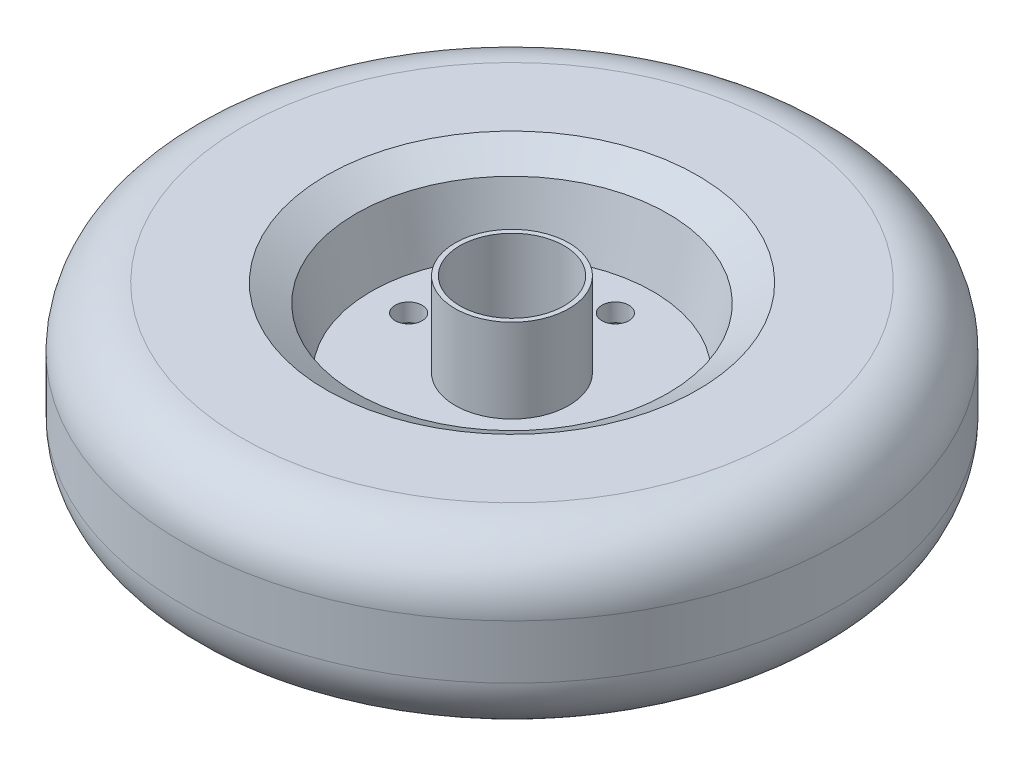
SolidWorks part; units mm, degrees
ref_plane "Alzado" through (0, 0, 0) normal (0, 0, 1) x (1, 0, 0)
ref_plane "Planta" through (0, 0, 0) normal (0, 1, 0) x (1, 0, 0)
ref_plane "Vista lateral" through (0, 0, 0) normal (1, 0, 0) x (0, 0, -1)
sketch "Croquis2" plane through (0, 0, 0) normal (0, 0, 1) x (1, 0, 0)
  line L0 (0, 31) -> (19, 31)
  line L1 (19, 31) -> (19, 3)
  line L2 (19, 3) -> (47, 3)
  line L3 (47, 3) -> (52, 23)
  line L4 (52, 23) -> (62, 29)
  line L5 (62, 29) -> (90, 29)
  line L6 (110, 9) -> (110, -9)
  line L7 (110, 0) -> (0, 0)
  line L8 (0, -31) -> (0, 31)
  line L9 (0, 64.7683) -> (0, -22.9111) construction
  line L10 (-41.779, 0) -> (154.4253, 0) construction
  line L11 (62, -29) -> (90, -29)
  line L12 (52, -23) -> (62, -29)
  line L13 (47, -3) -> (52, -23)
  line L14 (19, -3) -> (47, -3)
  line L15 (19, -31) -> (19, -3)
  line L16 (0, -31) -> (19, -31)
  arc A0 (90, 29) -> (110, 9) centre (90, 9) cw
  arc A1 (90, -29) -> (110, -9) centre (90, -9) ccw
  point P11 (110, 29)
  point P26 (110, -29)
  dimension "D10" = 20
  dimension "D1" = 19
  dimension "D2" = 28
  dimension "D3" = 48
  dimension "D4" = 10
  dimension "D5" = 5
  dimension "D6" = 29
  dimension "D7" = 28
  dimension "D8" = 3
  dimension "D9" = 20
revolve "Revolución1" add sketch "Croquis2" angle 360 about L9 region at (59.5227, 13.5557, 0) region at (59.5227, -13.5557, 0)
hole_wizard "Taladro de margen para M101" positions "Croquis3" profile "Croquis4" hole size "M10" standard "ISO" end condition through all
sketch "Croquis3" plane through (0, 31, 0) normal (0, 1, 0) x (1, 0, 0)
  point P0 (0, 0)
sketch "Croquis4" plane through (0, 31, 0) normal (1, 0, 0) x (0, 0, 1)
  line L0 (0, 0) -> (0, 62)
  line L1 (0, 62) -> (5.5, 62)
  line L2 (5.5, 62) -> (5.5, 0)
  line L5 (5.5, 0) -> (0, 0)
  line L11 (0, -6.35) -> (0, 107.95) construction
  dimension "Diámetro de taladro hasta el siguiente" = 11
  dimension "Profundidad de taladro hasta el siguiente" = 62
hole_wizard "Taladro de margen para M81" positions "Croquis5" profile "Croquis6" hole size "M8" standard "ISO" end condition through all
sketch "Croquis5" plane through (0, 3, 0) normal (0, 1, 0) x (1, 0, 0)
  point P0 (0, 34.5)
  dimension "D1" = 34.5
sketch "Croquis6" plane through (0, 3, -34.5) normal (1, 0, 0) x (0, 0, 1)
  line L0 (0, 0) -> (0, 34)
  line L1 (0, 34) -> (4.5, 34)
  line L2 (4.5, 34) -> (4.5, 0)
  line L5 (4.5, 0) -> (0, 0)
  line L11 (0, -6.35) -> (0, 107.95) construction
  dimension "Diámetro de taladro hasta el siguiente" = 9
  dimension "Profundidad de taladro hasta el siguiente" = 34
pattern_circular "MatrizC1" count 4 over 360 about axis through (0, 3, 0) along (0, 1, 0) of "Taladro de margen para M81"
sketch "Croquis8" plane through (0, 31, 0) normal (0, 1, 0) x (1, 0, 0)
  circle A0 centre (0, 0) radius 17.4
  circle A1 centre (0, 0) radius 19
  circle A2 centre (0, 0) radius 19
  dimension "D1" = 0
  dimension "D2" = 1.6
extrude "Cortar-Extruir2" cut sketch "Croquis8" against normal blind 50 contours A0
